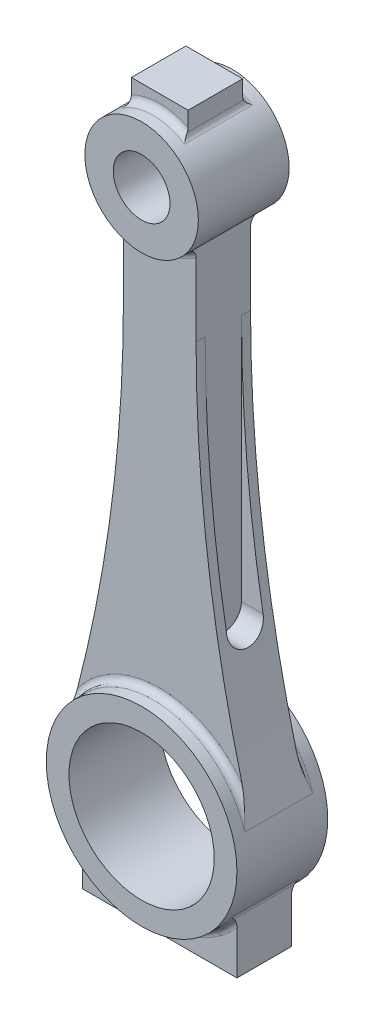
SolidWorks part; units mm, degrees
ref_plane "Front Plane" through (0, 0, 0) normal (0, 0, 1) x (1, 0, 0)
ref_plane "Top Plane" through (0, 0, 0) normal (0, 1, 0) x (1, 0, 0)
ref_plane "Right Plane" through (0, 0, 0) normal (1, 0, 0) x (0, 0, -1)
sketch "Sketch1" plane through (0, 0, 0) normal (0, 0, 1) x (1, 0, 0)
  circle A0 centre (0, 0) radius 16
  circle A1 centre (0, 0) radius 21
  circle A2 centre (0, 120) radius 6.25
  circle A3 centre (0, 120) radius 12.5
  dimension "D1" = 42
  dimension "D2" = 32
  dimension "D3" = 12.5
  dimension "D4" = 25
  dimension "D5" = 120
extrude "Boss-Extrude1" add sketch "Sketch1" along normal mid plane 20
sketch "Sketch2" plane through (0, 0, 0) normal (0, 0, 1) x (1, 0, 0)
  line L0 (8, 110.3953) -> (8, 92.5238)
  line L1 (0, 120) -> (0, 94.4653) construction
  line L2 (-8, 110.3953) -> (-8, 92.5238)
  circle A0 centre (0, 120) radius 12.5 construction
  circle A1 centre (0, 0) radius 21 construction
  circle A2 centre (0, 120) radius 12.5
  circle A3 centre (0, 0) radius 21
  arc A4 (8, 92.5238) -> (20.1869, 5.7869) centre (322.7562, 92.5238) ccw
  arc A5 (-8, 92.5238) -> (-20.1869, 5.7869) centre (-322.7562, 92.5238) cw
  point P8 (8, 101.4596)
  dimension "D1" = 8
extrude "Boss-Extrude2" add sketch "Sketch2" along normal mid plane 12 contours L2 A5 A3 A4 L0 A2 region at (0, 56.8897, 0)
sketch "Sketch3" plane through (0, 0, 0) normal (0, 0, 1) x (1, 0, 0)
  line L0 (0, -18.1664) -> (0, -30.1664) construction
  line L1 (-6.25, 135.8253) -> (-6.25, 130.8253)
  line L2 (6.25, 135.8253) -> (6.25, 130.8253)
  line L3 (-6.25, 135.8253) -> (6.25, 135.8253)
  line L4 (0, 157.2404) -> (0, -73.5331) construction
  line L5 (-17, -24.3288) -> (-17, -12.3288)
  line L6 (17, -24.3288) -> (17, -12.3288)
  line L7 (-17, -24.3288) -> (17, -24.3288)
  circle A0 centre (0, 120) radius 12.5 construction
  arc A1 (0, 107.5) -> (-6.25, 130.8253) centre (0, 120) ccw
  circle A2 centre (0, 0) radius 21 construction
  circle A3 centre (0, 0) radius 21
  dimension "D1" = 5
  dimension "D2" = 12.5
  dimension "D3" = 12
  dimension "D4" = 34
extrude "Boss-Extrude3" add sketch "Sketch3" along normal mid plane 12 contours A3 L5 L7 L6 | A1 L2 L3 L1 region at (0, 133.8599, 0) region at (-16.6394, -18.3288, 0)
fillet "Fillet1" radius 1.5 7 edges at (0, 21, -6) (0, 107.5, -6) (0, 107.5, 6) (6.25, 130.8253, 0) (0, 132.5, 6) (0, 132.5, -6) (-6.25, 130.8253, 0)
fillet "Fillet2" radius 1.5 5 edges at (0, -21, -6) (17, -12.3288, 0) (0, -21, 6) (-17, -12.3288, 0) (0, 21, 6)
ref_plane "Plane1" through (6, 0, 0) normal (1, 0, 0) x (0, 0, -1)
sketch "Sketch5" plane through (8, 0, 0) normal (1, 0, 0) x (0, 0, -1)
  line L0 (0, 38) -> (0, 100) construction
  line L1 (-4, 38) -> (-4, 100)
  line L2 (4, 38) -> (4, 100)
  line L3 (-10, 120) -> (10, 120) construction
  line L4 (-10, 132.5) -> (-10, 107.5) construction
  line L5 (10, 107.5) -> (10, 132.5) construction
  arc A0 (-4, 38) -> (4, 38) centre (0, 38) ccw
  arc A1 (4, 100) -> (-4, 100) centre (0, 100) ccw
  point P2 (0, 69)
  dimension "D1" = 4
  dimension "D2" = 62
  dimension "D3" = 20
extrude "Cut-Extrude1" cut sketch "Sketch5" along normal through all
mirror "Mirror4" about plane through (0, 0, 0) normal (1, 0, 0) of "Cut-Extrude1"
